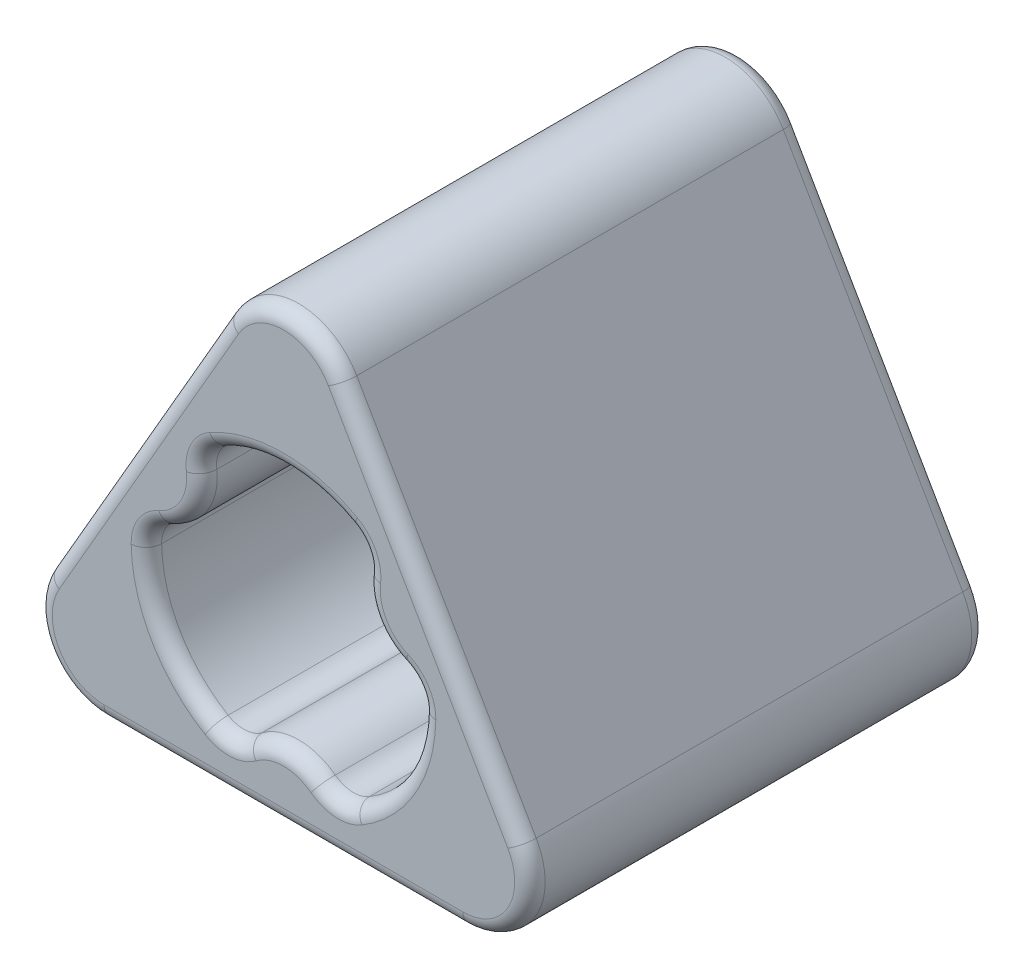
SolidWorks part; units mm, degrees
ref_plane "정면" through (0, 0, 0) normal (0, 0, 1) x (1, 0, 0)
ref_plane "윗면" through (0, 0, 0) normal (0, 1, 0) x (1, 0, 0)
ref_plane "우측면" through (0, 0, 0) normal (1, 0, 0) x (0, 0, -1)
sketch "스케치1" plane through (0, 0, 0) normal (0, 0, 1) x (1, 0, 0)
  line L0 (0, 11.2) -> (-9.6995, -5.6)
  line L1 (-9.6995, -5.6) -> (9.6995, -5.6)
  line L2 (9.6995, -5.6) -> (0, 11.2)
  line L3 (0, 11.2) -> (0, -5.6) construction
  line L4 (-9.6995, -5.6) -> (4.8497, 2.8) construction
  line L5 (9.6995, -5.6) -> (-4.8497, 2.8) construction
  circle A0 centre (0, 0) radius 4.5
  circle A1 centre (4.6765, 2.7) radius 2
  circle A2 centre (0, -5.4) radius 2
  circle A3 centre (-4.6765, 2.7) radius 2
  point P4 (0, 0)
  point P5 (0, -5.6)
  dimension "D2" = 9
  dimension "D3" = 4
  dimension "D1" = 16.8
  dimension "D4" = 0.2
  dimension "D5" = 0.2
  dimension "D6" = 0.2
extrude "보스-돌출1" add sketch "스케치1" along normal blind 15 contours A3 L0 L1 A2 A0 | A2 L1 L2 A1 A0 | A3 A0 A1 L2 L0 | A0 A3 L0 | L2 A1 A0 | A0 A2 L1 | A0 A3 | A0 A1 | A0 A2 region at (0, 6.5067, 0) region at (-4.3369, 2.5039, 0) region at (4.3369, 2.5039, 0) region at (-5.6349, -3.2533, 0) region at (-3.4579, 1.9964, 0) region at (5.6349, -3.2533, 0) region at (3.4579, 1.9964, 0) region at (0, -5.0078, 0) region at (0, -3.9929, 0)
fillet "필렛1" radius 2.2 3 edges at (-9.6995, -5.6, 7.5) (9.6995, -5.6, 7.5) (0, 11.2, 7.5)
fillet "필렛2" radius 1 6 edges at (2.8396, 3.491, 7.5) (4.443, 0.7137, 7.5) (1.6035, -4.2046, 7.5) (-1.6035, -4.2046, 7.5) (-4.443, 0.7137, 7.5) (-2.8396, 3.491, 7.5)
fillet "필렛3" radius 0.5 36 edges at (7.7942, -4.5, 0) (0, -5.6, 0) (-7.7942, -4.5, 0) (-4.8497, 2.8, 0) (0, 9, 0) (7.7942, -4.5, 15) (0, -5.6, 15) (-7.7942, -4.5, 15) (-4.8497, 2.8, 15) (0, 9, 15) (4.8497, 2.8, 0) (4.8497, 2.8, 15) (0, 4.5, 0) (2.589, 3.5149, 0) (2.9445, 1.7, 0) (4.3385, 0.4846, 0) (3.8971, -2.25, 0) (1.7495, -3.9996, 0) (0, -3.4, 0) (-1.7495, -3.9996, 0) (-3.8971, -2.25, 0) (-4.3385, 0.4846, 0) (-2.9445, 1.7, 0) (-4.3385, 0.4846, 15) (-3.8971, -2.25, 15) (-1.7495, -3.9996, 15) (0, -3.4, 15) (1.7495, -3.9996, 15) (3.8971, -2.25, 15) (4.3385, 0.4846, 15) (2.9445, 1.7, 15) (2.589, 3.5149, 15) (0, 4.5, 15) (-2.589, 3.5149, 15) (-2.589, 3.5149, 0) (-2.9445, 1.7, 15)
ref_axis "기준축1" through (-8.8979, 0, 0) along (1, 0, 0)
ref_axis "기준축2" through (0, 9.73, 0) along (0, -1, 0)
ref_axis "기준축3" through (0, 0, -0.75) along (0, 0, 1)
